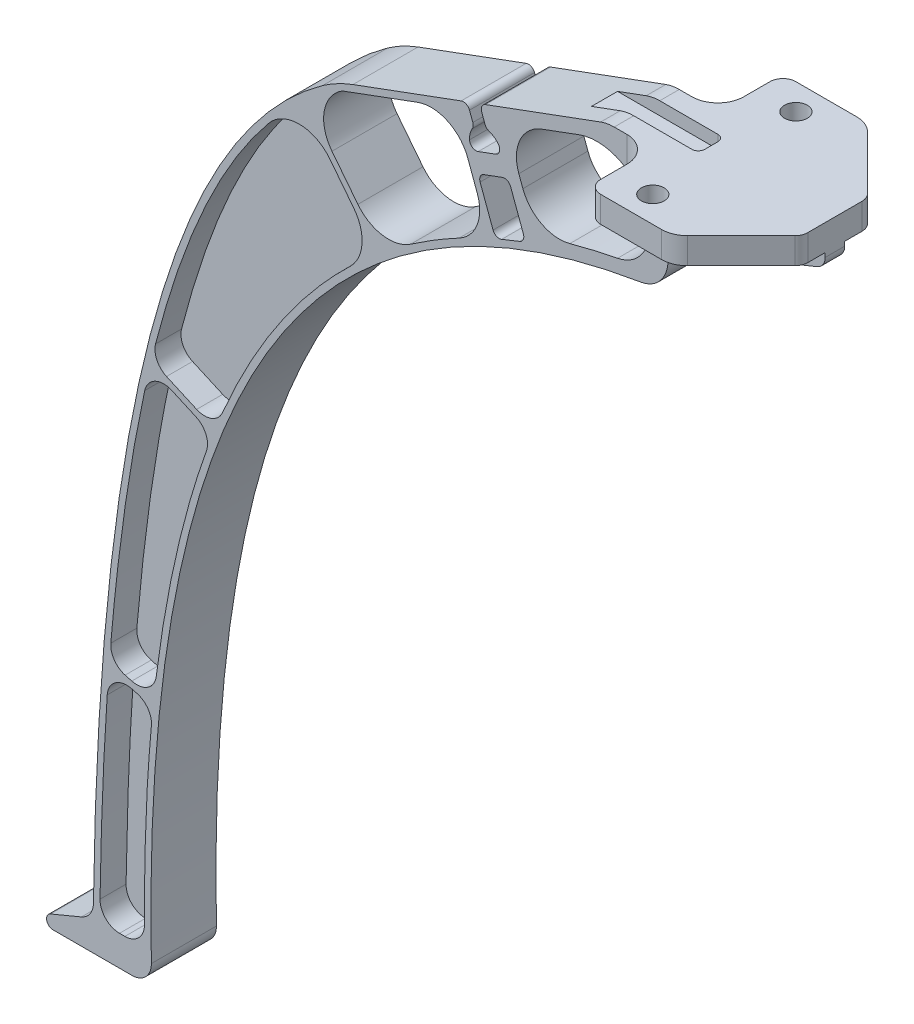
SolidWorks part; units mm, degrees
ref_plane "Front Plane" through (0, 0, 0) normal (0, 0, 1) x (1, 0, 0)
ref_plane "Top Plane" through (0, 0, 0) normal (0, 1, 0) x (1, 0, 0)
ref_plane "Right Plane" through (0, 0, 0) normal (1, 0, 0) x (0, 0, -1)
sketch "Sketch2" plane through (0, 0, 0) normal (0, 1, 0) x (1, 0, 0)
  line L0 (0, -15) -> (0, 15)
  line L1 (0, 15) -> (13, 15)
  line L2 (13, 15) -> (23, 5)
  line L3 (23, 5) -> (23, -5)
  line L4 (0, 0) -> (42.0863, 0) construction
  line L5 (13, -15) -> (23, -5)
  line L6 (0, -15) -> (13, -15)
  circle A0 centre (6, -11) radius 1.75
  circle A1 centre (6, 11) radius 1.75
  point P8 (23, 0)
  dimension "D5" = 3.5
  dimension "D6" = 22
  dimension "D7" = 6
  dimension "D1" = 30
  dimension "D2" = 10
  dimension "D3" = 13
  dimension "D4" = 45
extrude "Boss-Extrude1" add sketch "Sketch2" along normal blind 4
sketch "Sketch3" plane through (0, 0, 0) normal (0, 0, 1) x (1, 0, 0)
  line L0 (0, 4) -> (-7, 4)
  line L1 (-7, 4) -> (-48.1619, -11.1892)
  line L2 (0, 4) -> (0, 0)
  line L3 (0, 0) -> (2.3376, 0)
  line L4 (0, 0) -> (13, 0) construction
  line L5 (2.3376, 0) -> (2.3376, -14)
  line L6 (2.3376, -14) -> (-80.6065, -24.3779) construction
  line L7 (-80.6065, -24.3779) -> (-77, -146) construction
  line L8 (-48.1619, -11.1892) -> (-84.9453, -33.3694) construction
  line L9 (-84.9453, -33.3694) -> (-86, -141.3356) construction
  line L10 (-86, -141.3356) -> (-97.1832, -146)
  line L11 (-97.1832, -146) -> (-77, -146)
  line L12 (0, 4) -> (13, 4) construction
  line L13 (23, 4) -> (23, 0) construction
  spline S0 degree 2 poles (2.3376, -14) (-80.6065, -24.3779) (-77, -146) knots 0 0 0 1 1 1
  spline S1 degree 2 poles (-48.1619, -11.1892) (-84.9453, -33.3694) (-86, -141.3356) knots 0 0 0 1 1 1
  dimension "D1" = 150
  dimension "D2" = 100
  dimension "D3" = 9
  dimension "D4" = 18
  dimension "D5" = 30
extrude "Boss-Extrude2" add sketch "Sketch3" along normal mid plane 10
fillet "Fillet1" radius 1 1 edges at (-97.1832, -146, 0)
sketch "Sketch4" plane through (0, 0, 5) normal (0, 0, 1) x (1, 0, 0)
  line L0 (-85, -141.3454) -> (-78.1071, -141.3454)
  line L2 (-83.5908, -106.9092) -> (-76.8236, -108.742)
  spline S0 degree 3 poles (2872.2535, -2736.1952) (897.7141, -1323.4472) (103.4125, 143.6159) (-58.725, -21.4621) (-61.1898, -24.5952) (-68.0535, -35.3466) (-71.9197, -44.3183) (-78.1861, -65.8718) (-80.5867, -78.4519) (-120.9193, -427.8669) (242.6499, -1738.6491) (1042.0062, -3973.0285) knots -7.430102 -7.430102 -7.430102 -7.430102 0.125 0.125 0.25 0.25 0.5 0.5 0.75 0.75 6.575994 6.575994 6.575994 6.575994 only from (-47.6455, -12.0455) to (-85, -141.3454)
  spline S1 degree 3 poles (-83.5908, -106.9092) (-84.4096, -117.5438) (-84.8797, -129.0229) (-85, -141.3454) knots 0.828533 0.828533 0.828533 0.828533 1 1 1 1
  spline S2 degree 3 poles (1742.9052, -3697.8562) (502.7249, -1585.1585) (-133.4747, -399.4273) (-71.3532, -76.227) (-66.5107, -62.7958) (-56.4835, -46.1128) (-52.6805, -41.13) (-44.1543, -32.3324) (-39.4313, -28.5181) (-29.0762, -22.0677) (-23.4446, -19.4318) (240.5676, 69.4569) (1304.4417, -903.6373) (2942.9312, -2696.6446) knots -4.638 -4.638 -4.638 -4.638 0.25 0.25 0.5 0.5 0.625 0.625 0.75 0.75 0.875 0.875 6.178352 6.178352 6.178352 6.178352 only from (-77.9996, -146.0296) to (2.2135, -13.0077)
  spline S5 degree 3 poles (-78.1071, -141.3454) (-78.2954, -129.6939) (-77.8684, -118.8265) (-76.8236, -108.742) knots 0.019374 0.019374 0.019374 0.019374 0.165234 0.165234 0.165234 0.165234
  point P3 (-89.8993, -104.1646)
  point P8 (-69.7559, -109.6201)
  dimension "D1" = 1
  dimension "D2" = 1
extrude "Cut-Extrude1" cut sketch "Sketch4" against normal blind 4
fillet "Fillet2" radius 3 4 edges
fillet "Fillet3" radius 3 2 edges at (-86, -141.3356, 0) (-77, -146, 0)
sketch "Sketch5" plane through (0, 0, 5) normal (0, 0, 1) x (1, 0, 0)
  line L0 (-83.5114, -105.8947) -> (-76.717, -107.7348)
  line L4 (-77.2801, -63.5782) -> (-67.6478, -67.8666)
  line L6 (-79.2723, -108.0788) -> (-80.0781, -107.8606) construction
  line L7 (-79.2723, -108.0788) -> (-80.0781, -107.8606) construction
  spline S0 degree 3 poles (1738.9669, -3696.6582) (500.4545, -1581.1527) (-135.9483, -394.8293) (-70.9025, -74.8161) (-66.0067, -61.6985) (-55.9683, -45.4004) (-52.1731, -40.5316) (-43.6859, -31.9331) (-38.9941, -28.2039) (-28.7248, -21.8941) (-23.1476, -19.3137) (241.1801, 68.8684) (1304.7147, -904.0108) (2944.2158, -2695.4797) knots -4.710439 -4.710439 -4.710439 -4.710439 0.25 0.25 0.5 0.5 0.625 0.625 0.75 0.75 0.875 0.875 6.244296 6.244296 6.244296 6.244296 only from (-78.0772, -142.9582) to (2.2135, -13.0077)
  spline S1 degree 3 poles (-76.717, -107.7348) (-76.0514, -101.5861) (-75.1538, -95.7314) (-72.3872, -82.1202) (-70.263, -74.6849) (-67.6478, -67.8666) knots 0.159457 0.159457 0.159457 0.159457 0.25 0.25 0.381074 0.381074 0.381074 0.381074
  spline S2 degree 3 poles (2875.8173, -2732.2458) (896.9926, -1321.9378) (103.5591, 143.0755) (-58.6314, -21.3557) (-61.0784, -24.4479) (-67.8985, -35.0518) (-71.749, -43.8922) (-78.0111, -65.1174) (-80.4232, -77.5007) (-121.7676, -424.7127) (241.5393, -1735.5242) (1042.7105, -3970.7715) knots -7.494241 -7.494241 -7.494241 -7.494241 0.125 0.125 0.25 0.25 0.5 0.5 0.75 0.75 6.635612 6.635612 6.635612 6.635612 only from (-47.6455, -12.0455) to (-84.9778, -139.3785)
  spline S3 degree 3 poles (-77.2801, -63.5782) (-79.2721, -71.9997) (-80.8824, -81.3572) (-82.6514, -96.2133) (-83.1193, -100.9622) (-83.5114, -105.8947) knots 0.568149 0.568149 0.568149 0.568149 0.75 0.75 0.830672 0.830672 0.830672 0.830672
  point P2 (-90.2125, -56.726)
  point P3 (-53.7444, -72.9618)
  point P8 (-65.104, -15.2471)
  point P9 (-32.6934, -53.01)
  point P10 (-65.8629, -15.8984)
  point P11 (-33.4522, -53.6613)
  point P12 (-90.6193, -57.6396)
  point P13 (-54.1511, -73.8754)
  dimension "D5" = 1
  dimension "D1" = 1
  dimension "D2" = 1
extrude "Cut-Extrude2" cut sketch "Sketch5" against normal blind 4
fillet "Fillet4" radius 3 4 edges
sketch "Sketch6" plane through (0, 0, 5) normal (0, 0, 1) x (1, 0, 0)
  line L1 (-53.8996, -16.6868) -> (-42.4857, -31.2333)
  line L2 (-69.8109, -65.8089) -> (-73.5353, -64.1508)
  line L3 (-67.2853, -66.9334) -> (-77.0433, -62.589)
  spline S0 degree 3 poles (2875.8173, -2732.2458) (896.9926, -1321.9378) (103.5591, 143.0755) (-58.6314, -21.3557) (-61.0784, -24.4479) (-67.8985, -35.0518) (-71.749, -43.8922) (-78.0111, -65.1174) (-80.4232, -77.5007) (-121.7676, -424.7127) (241.5393, -1735.5242) (1042.7105, -3970.7715) knots -7.494241 -7.494241 -7.494241 -7.494241 0.125 0.125 0.25 0.25 0.5 0.5 0.75 0.75 6.635612 6.635612 6.635612 6.635612 only from (-47.6455, -12.0455) to (-84.9778, -139.3785)
  spline S1 degree 3 poles (-53.8996, -16.6868) (-54.6162, -17.3278) (-55.3208, -17.9994) (-58.6314, -21.3557) (-61.0784, -24.4479) (-67.8985, -35.0518) (-71.749, -43.8922) (-75.644, -57.0942) (-76.3651, -59.7889) (-77.0433, -62.589) knots 0.091927 0.091927 0.091927 0.091927 0.125 0.125 0.25 0.25 0.5 0.5 0.560997 0.560997 0.560997 0.560997
  spline S2 degree 3 poles (1738.9669, -3696.6582) (500.4545, -1581.1527) (-135.9483, -394.8293) (-70.9025, -74.8161) (-66.0067, -61.6985) (-55.9683, -45.4004) (-52.1731, -40.5316) (-43.6859, -31.9331) (-38.9941, -28.2039) (-28.7248, -21.8941) (-23.1476, -19.3137) (241.1801, 68.8684) (1304.7147, -904.0108) (2944.2158, -2695.4797) knots -4.710439 -4.710439 -4.710439 -4.710439 0.25 0.25 0.5 0.5 0.625 0.625 0.75 0.75 0.875 0.875 6.244296 6.244296 6.244296 6.244296 only from (-78.0772, -142.9582) to (2.2135, -13.0077)
  spline S3 degree 3 poles (-67.2853, -66.9334) (-64.9935, -61.1081) (-62.3372, -55.7409) (-55.9683, -45.4004) (-52.1731, -40.5316) (-46.1901, -34.4701) (-44.3754, -32.8037) (-42.4857, -31.2333) knots 0.387079 0.387079 0.387079 0.387079 0.5 0.5 0.625 0.625 0.676237 0.676237 0.676237 0.676237
  dimension "D1" = 1
  dimension "D2" = 1
  dimension "D3" = 1
extrude "Cut-Extrude3" cut sketch "Sketch6" against normal blind 4
fillet "Fillet5" radius 3 2 edges
fillet "Fillet6" radius 6 2 edges
mirror "Mirror1" about plane through (0, 0, 0) normal (0, 0, 1) of "Fillet2", "Fillet4", "Fillet5", "Fillet6", "Cut-Extrude1", "Cut-Extrude2", "Cut-Extrude3"
sketch "Sketch7" plane through (0, 0, 5) normal (0, 0, 1) x (1, 0, 0)
  line L0 (-27.5809, -3.5946) -> (-19.2808, -26.0874) construction
  line L1 (-7, 4) -> (-48.1619, -11.1892) construction
  line L2 (-28.5191, -3.9408) -> (-27.4805, -6.7553)
  line L3 (-27.4805, -6.7553) -> (-28.8878, -7.2746)
  line L4 (-28.8878, -7.2746) -> (-27.8492, -10.089)
  line L5 (-27.8492, -10.089) -> (-23.1584, -8.3581)
  line L6 (-24.1969, -5.5436) -> (-23.1584, -8.3581)
  line L7 (-25.6042, -6.0629) -> (-24.1969, -5.5436)
  line L8 (-26.6428, -3.2484) -> (-25.6042, -6.0629)
  line L9 (-22.1977, -10.9614) -> (-26.8885, -12.6923)
  line L10 (-26.8885, -12.6923) -> (-24.1878, -20.0112)
  line L12 (-22.1977, -10.9614) -> (-19.5447, -18.151)
  line L20 (-27.8492, -10.089) -> (-26.8885, -12.6923) construction
  line L21 (-23.1584, -8.3581) -> (-22.1977, -10.9614) construction
  line L22 (-28.5191, -3.9408) -> (-26.6428, -3.2484)
  spline S0 degree 3 poles (1738.9669, -3696.6582) (500.4545, -1581.1527) (-135.9483, -394.8293) (-70.9025, -74.8161) (-66.0067, -61.6985) (-55.9683, -45.4004) (-52.1731, -40.5316) (-43.6859, -31.9331) (-38.9941, -28.2039) (-28.7248, -21.8941) (-23.1476, -19.3137) (241.1801, 68.8684) (1304.7147, -904.0108) (2944.2158, -2695.4797) knots -4.710439 -4.710439 -4.710439 -4.710439 0.25 0.25 0.5 0.5 0.625 0.625 0.75 0.75 0.875 0.875 6.244296 6.244296 6.244296 6.244296 only from (-78.0772, -142.9582) to (2.2135, -13.0077)
  spline S1 degree 3 poles (-24.1878, -20.0112) (-22.6715, -19.3499) (-21.1238, -18.7299) (-19.5447, -18.151) knots 0.824652 0.824652 0.824652 0.824652 0.858132 0.858132 0.858132 0.858132
  point P10 (-25.5038, -9.2236)
  point P18 (-20.779, -22.0276)
  point P19 (-24.5431, -11.8268)
  dimension "D1" = 2
  dimension "D2" = 6
  dimension "D3" = 5
  dimension "D4" = 3
  dimension "D5" = 1
extrude "Cut-Extrude4" cut sketch "Sketch7" against normal through all
fillet "Fillet7" radius 3 2 edges at (-24.1969, -5.5436, 0) (-28.8878, -7.2746, 0)
fillet "Fillet8" radius 1 6 edges at (-27.8492, -10.089, 0) (-23.1584, -8.3581, 0) (-27.4805, -6.7553, 0) (-25.6042, -6.0629, 0) (-28.5191, -3.9408, 0) (-26.6428, -3.2484, 0)
fillet "Fillet9" radius 1 4 edges at (-22.1977, -10.9614, 0) (-26.8885, -12.6923, 0)
sketch "Sketch8" plane through (0, 0, 5) normal (0, 0, 1) x (1, 0, 0)
  line L3 (-29.1111, -5.2251) -> (-47.7261, -12.0943)
  line L4 (-30.5183, -5.7444) -> (-47.7261, -12.0943)
  line L6 (-45.1695, -26.193) -> (-48.8555, -21.4953)
  line L7 (-41.7122, -30.5992) -> (-53.1459, -16.0275)
  line L9 (-27.4805, -13.9767) -> (-25.4904, -19.3698)
  line L10 (-30.5183, -5.7444) -> (-25.1038, -20.4174)
  spline S0 degree 3 poles (2246.134, -4558.481) (675.575, -1900.6572) (-143.9071, -433.9851) (-70.9025, -74.8161) (-66.0067, -61.6985) (-55.9683, -45.4004) (-52.1731, -40.5316) (-43.6859, -31.9331) (-38.9941, -28.2039) (-28.7248, -21.8941) (-23.1476, -19.3137) (274.8653, 80.106) (1595.7859, -1175.7548) (3614.4831, -3437.5513) knots -5.347972 -5.347972 -5.347972 -5.347972 0.25 0.25 0.5 0.5 0.625 0.625 0.75 0.75 0.875 0.875 6.944474 6.944474 6.944474 6.944474 only from (-78.0772, -142.9582) to (2.2135, -13.0077)
  spline S1 degree 3 poles (-41.7122, -30.5992) (-39.2217, -28.5855) (-36.6038, -26.7352) (-31.0711, -23.3357) (-28.1522, -21.7919) (-25.1038, -20.4174) knots 0.68319 0.68319 0.68319 0.68319 0.75 0.75 0.817881 0.817881 0.817881 0.817881
  spline S2 degree 3 poles (3705.7179, -3287.4669) (1118.0784, -1738.2554) (124.46, 164.9358) (-58.6881, -21.423) (-61.1298, -24.5182) (-67.9351, -35.1281) (-71.7771, -43.9685) (-78.0256, -65.1857) (-80.4325, -77.5609) (-126.9944, -469.0835) (345.1876, -2101.0455) (1385.1179, -4910.1232) knots -8.513967 -8.513967 -8.513967 -8.513967 0.125 0.125 0.25 0.25 0.5 0.5 0.75 0.75 7.424531 7.424531 7.424531 7.424531 only from (-47.7261, -12.0943) to (-84.9778, -139.3785)
  spline S3 degree 3 poles (-47.7261, -12.0943) (-49.6021, -13.2316) (-51.4084, -14.5421) (-53.1459, -16.0275) knots 0 0 0 0 0.079352 0.079352 0.079352 0.079352
  dimension "D1" = 1
  dimension "D2" = 1
  dimension "D3" = 1
  dimension "D4" = 1
extrude "Cut-Extrude5" cut sketch "Sketch8" against normal through all
fillet "Fillet10" radius 6 2 edges
fillet "Fillet11" radius 6 2 edges at (-30.5183, -5.7444, 0)
sketch "Sketch9" plane through (0, 0, 5) normal (0, 0, 1) x (1, 0, 0)
  line L2 (-6.3076, 2.1237) -> (-25.0122, -4.7785)
  line L3 (-6.6428, 2) -> (-22.6668, -3.913)
  line L5 (-18.0133, -16.5239) -> (-19.9752, -11.2071)
  line L6 (-18.0051, -16.5459) -> (-22.6668, -3.913)
  line L7 (-0.5631, 2) -> (-0.5631, -12.3785)
  line L8 (0, 2) -> (-7, 2)
  line L9 (-0.5631, 2) -> (-6.6428, 2)
  spline S0 degree 3 poles (1664.8137, -3735.7412) (506.9851, -1580.3351) (-137.3897, -396.9002) (-73.4337, -82.2485) (-71.4161, -75.0807) (-66.4739, -61.8573) (-63.5492, -55.8017) (-56.7826, -44.8157) (-52.9405, -39.8856) (-44.3419, -31.1742) (-39.5856, -27.3936) (-29.1804, -21.0003) (-23.5322, -18.3878) (256.1415, 74.9138) (1406.7871, -1013.9599) (2907.8115, -2730.5488) knots -4.717916 -4.717916 -4.717916 -4.717916 0.25 0.25 0.375 0.375 0.5 0.5 0.625 0.625 0.75 0.75 0.875 0.875 6.498189 6.498189 6.498189 6.498189 only from (-79.077, -142.9791) to (2.0893, -12.0155)
  spline S1 degree 3 poles (-18.0051, -16.5459) (-17.8206, -16.483) (-17.6357, -16.4207) (-12.1493, -14.5904) (-6.5189, -13.2649) (-0.5631, -12.3785) knots 0.871191 0.871191 0.871191 0.871191 0.875 0.875 0.983955 0.983955 0.983955 0.983955
  dimension "D1" = 2
  dimension "D2" = 2
  dimension "D3" = 2
  dimension "D4" = 2
extrude "Cut-Extrude6" cut sketch "Sketch9" against normal through all
fillet "Fillet12" radius 6 3 edges at (-22.6668, -3.913, 0)
fillet "Fillet13" radius 8 1 edges at (-0.5631, 2, 0)
fillet "Fillet14" radius 8 1 edges at (-6.6428, 2, 0)
sketch "Sketch10" plane through (0, 0, 0) normal (0, 0, 1) x (1, 0, 0)
  line L0 (23, 0) -> (23, -2)
  line L1 (23, -2) -> (2.3376, -10.3242)
  line L2 (2.3376, -10.3242) -> (2.3376, 0)
  line L3 (2.3376, 0) -> (23, 0)
  dimension "D1" = 2
extrude "Boss-Extrude3" add sketch "Sketch10" along normal mid plane 3
fillet "Fillet15" radius 2 1 edges at (23, -2, 0)
fillet "Fillet16" radius 5 1 edges at (2.3376, -14, 0)
fillet "Fillet17" radius 8 1 edges at (2.2922, -10.3425, 0)
fillet "Fillet18" radius 2 4 edges at (0, 2, -15) (0, 2, 15) (23, 2, -5) (23, 2, 5)
fillet "Fillet19" radius 4 2 edges at (0, 2, -5) (0, 2, 5)
fillet "Fillet20" radius 4 2 edges at (13, 2, -15) (13, 2, 15)
sketch "Sketch11" plane through (0, 4, 0) normal (0, 1, 0) x (1, 0, 0)
  line L0 (0, 0) -> (-14.8789, 0) construction
  line L1 (-14, -2) -> (4, -2)
  line L3 (4, -2) -> (4, 2)
  line L4 (-14, 2) -> (4, 2)
  line L5 (23, -4.1716) -> (23, 4.1716) construction
  line L6 (-14, -2) -> (-14, 2)
  point P10 (4, 0)
  dimension "D1" = 4
  dimension "D2" = 19
  dimension "D3" = 37
extrude "Cut-Extrude7" cut sketch "Sketch11" against normal blind 2
fillet "Fillet21" radius 6 2 edges at (-7, 4, 3.5) (-7, 4, -3.5)
fillet "Fillet22" radius 1 2 edges at (4, 3, 2) (4, 3, -2)
fillet "Fillet23" radius 5 2 edges at (2.3376, 0, -3.25) (2.3376, 0, 3.25)
fillet "Fillet24" radius 4 2 edges at (1.6688, 0, -5) (1.6688, 0, 5)
fillet "Fillet25" radius 20 1 edges at (-48.1619, -11.1892, 0)
